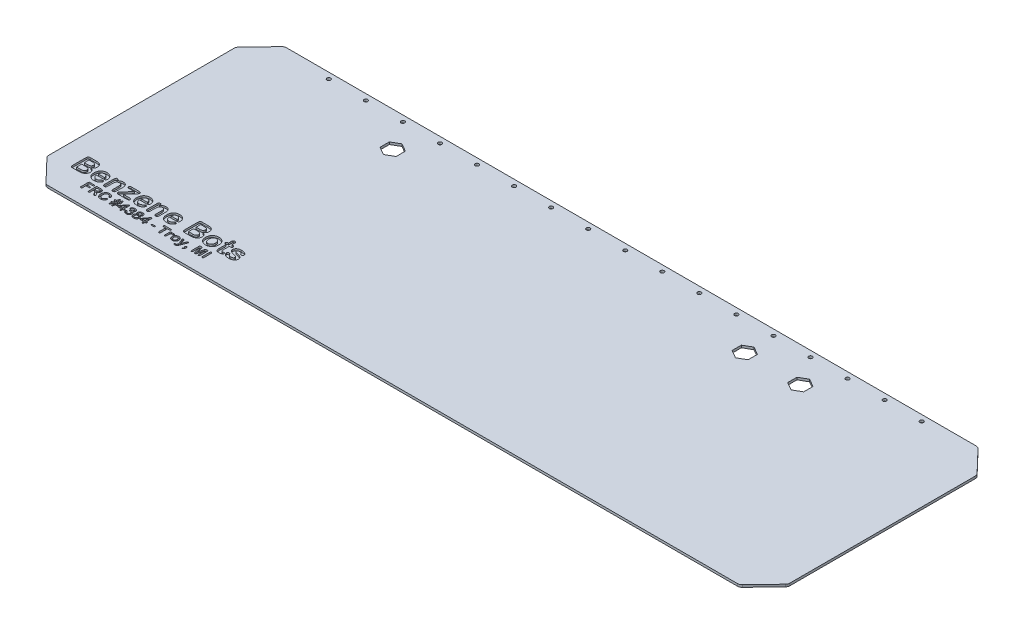
SolidWorks part; units mm, degrees
ref_plane "Front" through (0, 0, 0) normal (0, 0, 1) x (1, 0, 0)
ref_plane "Top" through (0, 0, 0) normal (0, 1, 0) x (1, 0, 0)
ref_plane "Right" through (0, 0, 0) normal (1, 0, 0) x (0, 0, -1)
sketch "Sketch1" plane through (0, 0, 0) normal (0, 1, 0) x (1, 0, 0)
  line L1 (6.35, 0) -> (1009.65, 0)
  line L2 (0, 6.35) -> (0, 320.675)
  line L3 (6.35, 327.025) -> (1009.65, 327.025)
  line L4 (1016, 6.35) -> (1016, 320.675)
  line L5 (0, 0) -> (1016, 327.025) construction
  line L6 (0, 327.025) -> (1016, 0) construction
  arc A0 (1009.65, 327.025) -> (1016, 320.675) centre (1009.65, 320.675) cw
  arc A1 (1009.65, 0) -> (1016, 6.35) centre (1009.65, 6.35) ccw
  arc A2 (6.35, 0) -> (0, 6.35) centre (6.35, 6.35) cw
  arc A3 (0, 320.675) -> (6.35, 327.025) centre (6.35, 320.675) cw
  point P4 (508, 163.5125)
  dimension "D1" = 327.025
  dimension "D2" = 1016
extrude "Base" add sketch "Sketch1" along normal blind 3.175
sketch "Sketch2" plane through (0, 3.175, 0) normal (0, 1, 0) x (1, 0, 0)
  line L0 (279.4, 327.025) -> (279.4, 0) construction
  line L1 (1009.65, 327.025) -> (6.35, 327.025) construction
  line L2 (6.35, 0) -> (1009.65, 0) construction
  line L3 (0, 320.675) -> (0, 6.35) construction
  line L4 (736.6, 327.025) -> (736.6, 0) construction
  line L5 (508, 318.77) -> (508, 327.025) construction
  circle A0 centre (508, 318.77) radius 2.54
  circle A1 centre (457.2, 318.77) radius 2.54
  circle A2 centre (406.4, 318.77) radius 2.54
  circle A3 centre (355.6, 318.77) radius 2.54
  circle A4 centre (304.8, 318.77) radius 2.54
  circle A5 centre (254, 318.77) radius 2.54
  circle A6 centre (203.2, 318.77) radius 2.54
  circle A7 centre (152.4, 318.77) radius 2.54
  circle A8 centre (558.8, 318.77) radius 2.54
  circle A9 centre (609.6, 318.77) radius 2.54
  circle A10 centre (660.4, 318.77) radius 2.54
  circle A11 centre (711.2, 318.77) radius 2.54
  circle A12 centre (762, 318.77) radius 2.54
  circle A13 centre (812.8, 318.77) radius 2.54
  circle A14 centre (863.6, 318.77) radius 2.54
  circle A15 centre (101.6, 318.77) radius 2.54
  circle A16 centre (914.4, 318.77) radius 2.54
  point P43 (557.4422, 322.0286)
  dimension "D3" = 8.255
  dimension "D4" = 5.08
  dimension "D1" = 279.4
  dimension "D2" = 736.6
  dimension "D7" = 50.8
  dimension "D8" = 50.8
  dimension "D5" = 9
  dimension "D6" = 9
extrude "Hinge Holes" cut sketch "Sketch2" against normal up to next
sketch "Sketch3" plane through (0, 3.175, 0) normal (0, 1, 0) x (1, 0, 0)
  line L0 (1.7649, 294.8705) -> (30.6983, 325.0681)
  line L1 (0, 320.675) -> (0, 6.35) construction
  line L2 (1009.65, 327.025) -> (6.35, 327.025) construction
  line L3 (508, 327.025) -> (508, 0) construction
  line L4 (6.35, 0) -> (1009.65, 0) construction
  line L5 (0, 163.5125) -> (1016, 163.5125) construction
  line L6 (1016, 6.35) -> (1016, 320.675) construction
  line L11 (1016, 290.4774) -> (1016, 327.025)
  line L12 (980.7167, 327.025) -> (1016, 327.025)
  line L13 (35.2833, 327.025) -> (0, 327.025)
  line L14 (0, 290.4774) -> (0, 327.025)
  line L25 (1014.2351, 294.8705) -> (985.3017, 325.0681)
  line L26 (1014.2351, 32.1545) -> (985.3017, 1.9569)
  line L27 (0, 36.5476) -> (0, 0)
  line L28 (35.2833, 0) -> (0, 0)
  line L29 (980.7167, 0) -> (1016, 0)
  line L30 (1016, 36.5476) -> (1016, 0)
  line L31 (1.7649, 32.1545) -> (30.6983, 1.9569)
  arc A3 (30.6983, 325.0681) -> (35.2833, 327.025) centre (35.2833, 320.675) cw
  arc A4 (1.7649, 294.8705) -> (0, 290.4774) centre (6.35, 290.4774) ccw
  arc A5 (1014.2351, 294.8705) -> (1016, 290.4774) centre (1009.65, 290.4774) cw
  arc A6 (985.3017, 325.0681) -> (980.7167, 327.025) centre (980.7167, 320.675) ccw
  arc A7 (985.3017, 1.9569) -> (980.7167, 0) centre (980.7167, 6.35) cw
  arc A8 (1014.2351, 32.1545) -> (1016, 36.5476) centre (1009.65, 36.5476) ccw
  arc A9 (1.7649, 32.1545) -> (0, 36.5476) centre (6.35, 36.5476) cw
  arc A10 (30.6983, 1.9569) -> (35.2833, 0) centre (35.2833, 6.35) ccw
  point P18 (0, 0)
  point P27 (0, 0)
  point P33 (35.2833, 327.025)
  point P36 (0, 290.4774)
  dimension "D1" = 6.35
  dimension "D2" = 50.8
extrude "Corner Cut" cut sketch "Sketch3" against normal up to next
sketch "Sketch4" plane through (0, 3.175, 0) normal (0, 1, 0) x (1, 0, 0)
  line L0 (279.4, 0) -> (279.4, 327.025) construction
  line L1 (35.2833, 0) -> (980.7167, 0) construction
  line L2 (980.7167, 327.025) -> (35.2833, 327.025) construction
  line L3 (736.6, 0) -> (736.6, 327.025) construction
  line L4 (0, 290.4774) -> (0, 36.5476) construction
  line L5 (260.35, 0) -> (260.35, 327.025) construction
  line L6 (755.65, 0) -> (755.65, 327.025) construction
  dimension "D1" = 279.4
  dimension "D2" = 736.6
  dimension "D3" = 19.05
  dimension "D4" = 19.05
sketch "Sketch5" plane through (0, 3.175, 0) normal (0, 1, 0) x (1, 0, 0)
  text T0 "Benzene Bots" font "Arial Rounded MT Bold" height 25.4
  text T1 "FRC #4384 - Troy, MI" font "Arial Rounded MT Bold" height 12.7
  point P1 (29.8314, 280.3436)
  point P2 (0, 0)
  point P4 (58.8294, 260.268)
  point P5 (0, 0)
  point P6 (0, 0)
  point P7 (0, 0)
  point P8 (0, 0)
  point P9 (64.7343, 20.5382)
  point P10 (30.3861, 48.5893)
  point P11 (35.3024, 39.2929)
  point P12 (60.5583, 20.1255)
  point P13 (30.567, 37.7144)
  point P14 (0, 0)
  point P15 (0, 0)
  point P16 (0, 0)
  point P17 (0, 0)
extrude "Text" cut sketch "Sketch5" against normal blind 2.54
sketch "Sketch6" plane through (0, 3.175, 0) normal (0, 1, 0) x (1, 0, 0)
  line L0 (508, 0) -> (508, 327.025) construction
  line L1 (228.6, 292.1) -> (217.6015, 285.75)
  line L2 (217.6015, 285.75) -> (217.6015, 273.05)
  line L3 (217.6015, 273.05) -> (228.6, 266.7)
  line L4 (228.6, 266.7) -> (239.5985, 273.05)
  line L5 (239.5985, 273.05) -> (239.5985, 285.75)
  line L6 (239.5985, 285.75) -> (228.6, 292.1)
  line L7 (35.2833, 0) -> (980.7167, 0) construction
  line L8 (980.7167, 327.025) -> (35.2833, 327.025) construction
  line L9 (776.4015, 285.75) -> (787.4, 292.1)
  line L10 (776.4015, 273.05) -> (776.4015, 285.75)
  line L11 (787.4, 266.7) -> (776.4015, 273.05)
  line L12 (798.3985, 273.05) -> (787.4, 266.7)
  line L13 (798.3985, 285.75) -> (798.3985, 273.05)
  line L14 (787.4, 292.1) -> (798.3985, 285.75)
  line L16 (700.2015, 273.05) -> (711.2, 266.7)
  line L17 (711.2, 266.7) -> (722.1985, 273.05)
  line L18 (722.1985, 273.05) -> (722.1985, 285.75)
  line L19 (722.1985, 285.75) -> (711.2, 292.1)
  line L20 (711.2, 292.1) -> (700.2015, 285.75)
  line L21 (700.2015, 285.75) -> (700.2015, 273.05)
  circle A0 centre (228.6, 279.4) radius 10.9985 construction
  circle A1 centre (787.4, 279.4) radius 10.9985 construction
  circle A2 centre (711.2, 279.4) radius 10.9985 construction
  point P23 (0, 0)
  point P31 (0, 0)
  point P32 (0, 0)
  point P33 (0, 0)
extrude "Cut-Extrude4" cut sketch "Sketch6" against normal up to next
